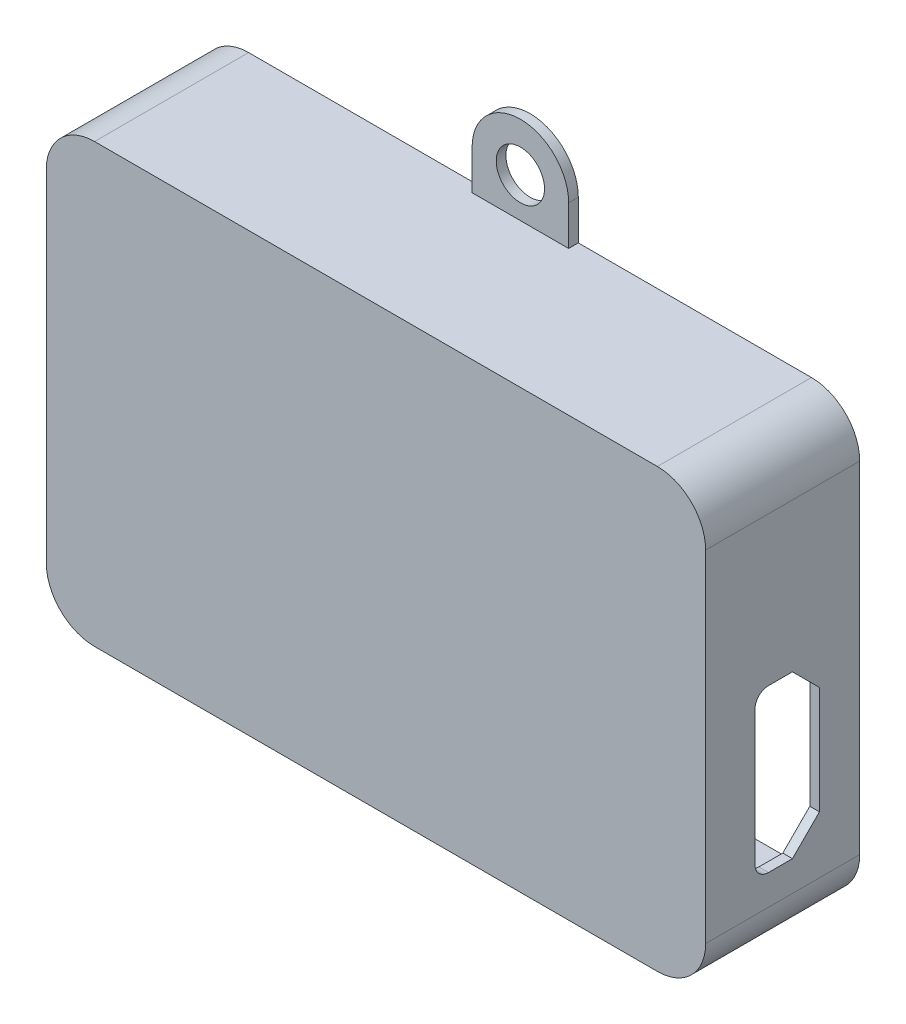
SolidWorks part; units mm, degrees
ref_plane "Front Plane" through (0, 0, 0) normal (0, 0, 1) x (1, 0, 0)
ref_plane "Top Plane" through (0, 0, 0) normal (0, 1, 0) x (1, 0, 0)
ref_plane "Right Plane" through (0, 0, 0) normal (1, 0, 0) x (0, 0, -1)
sketch "Sketch1" plane through (0, 0, 0) normal (0, 0, 1) x (1, 0, 0)
  line L1 (-14.575, -11.325) -> (14.575, -11.325)
  line L2 (-17.075, -8.825) -> (-17.075, 8.825)
  line L3 (-14.575, 11.325) -> (14.575, 11.325)
  line L4 (17.075, -8.825) -> (17.075, 8.825)
  line L5 (-17.075, -11.325) -> (17.075, 11.325) construction
  line L6 (-17.075, 11.325) -> (17.075, -11.325) construction
  line L8 (-16.575, 10.825) -> (-17.075, 10.825) construction
  line L9 (14.575, -10.825) -> (-14.575, -10.825)
  line L10 (16.575, -8.825) -> (16.575, 8.825)
  line L11 (14.575, 10.825) -> (-14.575, 10.825)
  line L12 (-16.575, -8.825) -> (-16.575, 8.825)
  line L13 (16.575, -10.825) -> (-16.575, 10.825) construction
  line L14 (16.575, 10.825) -> (-16.575, -10.825) construction
  line L15 (-16.575, 10.825) -> (-16.575, 11.325) construction
  line L16 (-16.375, 9.825) -> (-16.375, -9.825) construction
  line L17 (16.375, 9.825) -> (-16.375, 9.825) construction
  line L18 (-2.5, 13.375) -> (-2.5, 11.325)
  line L19 (2.5, 13.375) -> (2.5, 11.325)
  line L20 (-2.5, -13.375) -> (-2.5, -11.325)
  line L21 (2.5, -13.375) -> (2.5, -11.325)
  line L22 (-20.75, 2.5) -> (-17.075, 2.5)
  line L23 (-20.75, -2.5) -> (-17.075, -2.5)
  arc A0 (-14.575, -10.825) -> (-16.575, -8.825) centre (-14.575, -8.825) cw
  arc A1 (-2.4744, -13.0179) -> (2.4744, -13.0179) centre (0, -13.375) ccw construction
  arc A2 (14.575, -10.825) -> (16.575, -8.825) centre (14.575, -8.825) ccw
  arc A3 (16.575, 8.825) -> (14.575, 10.825) centre (14.575, 8.825) ccw
  arc A4 (-20.3929, 2.4744) -> (-20.3929, -2.4744) centre (-20.75, 0) ccw construction
  arc A5 (-14.575, 10.825) -> (-16.575, 8.825) centre (-14.575, 8.825) ccw
  arc A6 (-14.575, -11.325) -> (-17.075, -8.825) centre (-14.575, -8.825) cw
  arc A7 (14.575, -11.325) -> (17.075, -8.825) centre (14.575, -8.825) ccw
  arc A8 (2.4744, 13.0179) -> (-2.4744, 13.0179) centre (0, 13.375) ccw construction
  circle A9 centre (-20.75, 0) radius 1.25
  arc A10 (-2.4744, -13.0179) -> (2.4744, -13.0179) centre (0, -13.375) ccw
  circle A11 centre (0, 13.375) radius 1.25
  circle A12 centre (0, -13.375) radius 1.25
  arc A13 (-20.3929, 2.4744) -> (-20.3929, -2.4744) centre (-20.75, 0) ccw
  arc A14 (14.575, 11.325) -> (17.075, 8.825) centre (14.575, 8.825) cw
  arc A15 (-17.075, 8.825) -> (-14.575, 11.325) centre (-14.575, 8.825) cw
  arc A17 (2.4744, 13.0179) -> (-2.4744, 13.0179) centre (0, 13.375) ccw
  point P0 (0, 0)
  point P31 (0, 0)
  dimension "D4" = 2.5
  dimension "D5" = 2
  dimension "D6" = 2.5
  dimension "D1" = 0.5
  dimension "D2" = 0.2
  dimension "D3" = 1
extrude "Boss-Extrude1" add sketch "Sketch1" along normal offset from surface (7.48 mm away) 2.5 contours A13 L2 | L1 L4 L3 L2 L9 L12 L11 L10 | A17 L3 | A10 L1 region at (-16.053, -10.303, 0) region at (0, -11.3926, 0) region at (-18.9125, -2.4205, 0) region at (-2.4324, 12.35, 0) offset beyond the face yes
sketch "Sketch2" plane through (0, 0, 7.48) normal (0, 0, 1) x (1, 0, 0)
  line L0 (-2.5, 11.325) -> (2.5, 11.325)
  line L1 (-17.075, 2.5) -> (-17.075, -2.5)
  line L2 (-2.5, -11.325) -> (2.5, -11.325)
  line L13 (-17.075, 2.5) -> (-20.75, 2.5)
  line L14 (-20.75, -2.5) -> (-17.075, -2.5)
  line L15 (-17.075, -2.5) -> (-17.075, -8.825)
  line L16 (-14.575, -11.325) -> (-2.5, -11.325)
  line L17 (-2.5, -11.325) -> (-2.5, -13.375)
  line L18 (2.5, -13.375) -> (2.5, -11.325)
  line L19 (2.5, -11.325) -> (14.575, -11.325)
  line L20 (17.075, -8.825) -> (17.075, 8.825)
  line L21 (14.575, 11.325) -> (2.5, 11.325)
  line L22 (2.5, 11.325) -> (2.5, 13.375)
  line L23 (-2.5, 13.375) -> (-2.5, 11.325)
  line L24 (-2.5, 11.325) -> (-14.575, 11.325)
  line L25 (-17.075, 8.825) -> (-17.075, 2.5)
  line L26 (-17.075, 2.5) -> (-20.75, 2.5)
  line L27 (-20.75, -2.5) -> (-17.075, -2.5)
  line L28 (-17.075, -2.5) -> (-17.075, -8.825)
  line L29 (-14.575, -11.325) -> (-2.5, -11.325)
  line L30 (-2.5, -11.325) -> (-2.5, -13.375)
  line L31 (2.5, -13.375) -> (2.5, -11.325)
  line L32 (2.5, -11.325) -> (14.575, -11.325)
  line L33 (17.075, -8.825) -> (17.075, 8.825)
  line L34 (14.575, 11.325) -> (2.5, 11.325)
  line L35 (2.5, 11.325) -> (2.5, 13.375)
  line L36 (-2.5, 13.375) -> (-2.5, 11.325)
  line L37 (-2.5, 11.325) -> (-14.575, 11.325)
  line L38 (-17.075, 8.825) -> (-17.075, 2.5)
  arc A7 (-20.75, 2.5) -> (-20.75, -2.5) centre (-20.75, 0) ccw
  arc A8 (-17.075, -8.825) -> (-14.575, -11.325) centre (-14.575, -8.825) ccw
  arc A9 (-2.5, -13.375) -> (2.5, -13.375) centre (0, -13.375) ccw
  arc A10 (14.575, -11.325) -> (17.075, -8.825) centre (14.575, -8.825) ccw
  arc A11 (17.075, 8.825) -> (14.575, 11.325) centre (14.575, 8.825) ccw
  arc A12 (2.5, 13.375) -> (-2.5, 13.375) centre (0, 13.375) ccw
  arc A13 (-14.575, 11.325) -> (-17.075, 8.825) centre (-14.575, 8.825) ccw
  arc A14 (-20.75, 2.5) -> (-20.75, -2.5) centre (-20.75, 0) ccw
  arc A15 (-17.075, -8.825) -> (-14.575, -11.325) centre (-14.575, -8.825) ccw
  arc A16 (-2.5, -13.375) -> (2.5, -13.375) centre (0, -13.375) ccw
  arc A17 (14.575, -11.325) -> (17.075, -8.825) centre (14.575, -8.825) ccw
  arc A18 (17.075, 8.825) -> (14.575, 11.325) centre (14.575, 8.825) ccw
  arc A19 (2.5, 13.375) -> (-2.5, 13.375) centre (0, 13.375) ccw
  arc A20 (-14.575, 11.325) -> (-17.075, 8.825) centre (-14.575, 8.825) ccw
  arc M18 (-20.75, 2.5) -> (-20.75, -2.5) centre (-20.75, 0) ccw
  arc M23 (-2.5, -13.375) -> (2.5, -13.375) centre (0, -13.375) ccw
  arc M29 (2.5, 13.375) -> (-2.5, 13.375) centre (0, 13.375) ccw
  circle M57 centre (0, 13.375) radius 1.25
  circle M62 centre (-20.75, 0) radius 1.25
  line M63 (-17.075, 2.5) -> (-20.75, 2.5)
  line M64 (-20.75, -2.5) -> (-17.075, -2.5)
  line M68 (-2.5, -11.325) -> (-2.5, -13.375)
  line M69 (2.5, -13.375) -> (2.5, -11.325)
  line M74 (2.5, 11.325) -> (2.5, 13.375)
  line M75 (-2.5, 13.375) -> (-2.5, 11.325)
  circle M79 centre (0, -13.375) radius 1.25
  dimension "D1" = 0
extrude "Cut-Extrude1" cut sketch "Sketch2" against normal offset from surface (6.98 mm away) 0.5 contours L0 M75 M74 M29 M57 | L1 M63 M18 M64 M62 | L2 M68 M23 M69 M79 region at (-2.4324, 12.35, 7.48) region at (-17.1545, 0, 7.48) region at (2.4324, -12.35, 7.48) up to face at (-3.9075, 0, 0)
sketch "Sketch3" plane through (17.075, 0, 0) normal (1, 0, 0) x (0, 0, -1)
  line L0 (-3.98, -7.065) -> (-4.18, -7.065) construction
  line L1 (-5.425, -7.265) -> (-2.085, -7.265)
  line L2 (-5.425, -7.265) -> (-5.425, 1.115)
  line L3 (-5.425, 1.115) -> (-2.085, 1.115)
  line L4 (-2.085, -7.265) -> (-2.085, 1.115)
  line L5 (-5.225, -6.075) -> (-5.425, -6.075) construction
  line L6 (-4.18, -7.065) -> (-4.18, -7.265) construction
  line L7 (-4.18, 0.915) -> (-4.18, 1.115) construction
  line L8 (-2.285, -5.375) -> (-2.085, -5.375) construction
  dimension "D1" = 0.2
extrude "Cut-Extrude2" cut sketch "Sketch3" against normal up to next
chamfer "Chamfer1" distance 1.4 angle 45 2 edges at (16.825, 1.115, 2.085) (16.825, -7.265, 2.085)
fillet "Fillet1" radius 0.7 2 edges at (16.825, 1.115, 5.425) (16.825, -7.265, 5.425)
sketch "Sketch4" plane through (0, 0, 7.48) normal (0, 0, 1) x (1, 0, 0)
  line L4 (-17.075, 8.825) -> (-17.075, -8.825)
  line L5 (-14.575, -11.325) -> (14.575, -11.325)
  line L6 (17.075, -8.825) -> (17.075, 8.825)
  line L7 (14.575, 11.325) -> (-14.575, 11.325)
  line L8 (-17.075, 8.825) -> (-17.075, -8.825)
  line L9 (-14.575, -11.325) -> (14.575, -11.325)
  line L10 (17.075, -8.825) -> (17.075, 8.825)
  line L11 (14.575, 11.325) -> (-14.575, 11.325)
  arc A4 (-17.075, -8.825) -> (-14.575, -11.325) centre (-14.575, -8.825) ccw
  arc A5 (14.575, -11.325) -> (17.075, -8.825) centre (14.575, -8.825) ccw
  arc A6 (17.075, 8.825) -> (14.575, 11.325) centre (14.575, 8.825) ccw
  arc A7 (-14.575, 11.325) -> (-17.075, 8.825) centre (-14.575, 8.825) ccw
  arc A8 (-17.075, -8.825) -> (-14.575, -11.325) centre (-14.575, -8.825) ccw
  arc A9 (14.575, -11.325) -> (17.075, -8.825) centre (14.575, -8.825) ccw
  arc A10 (17.075, 8.825) -> (14.575, 11.325) centre (14.575, 8.825) ccw
  arc A11 (-14.575, 11.325) -> (-17.075, 8.825) centre (-14.575, 8.825) ccw
  dimension "D1" = 0
extrude "Boss-Extrude2" add sketch "Sketch4" along normal blind 0.5
sketch "Sketch5" [suppressed] plane through (0, 0, 0.5) normal (0, 0, 1) x (1, 0, 0)
  line L0 (2.5, -13.375) -> (2.5, -11.325) construction
  line L1 (2.5, -11.325) -> (-2.5, -11.325) construction
  line L2 (-2.5, -11.325) -> (-2.5, -13.375) construction
  line L3 (-2.5, 13.375) -> (-2.5, 11.325) construction
  line L4 (-2.5, 11.325) -> (2.5, 11.325) construction
  line L5 (2.5, 11.325) -> (2.5, 13.375) construction
  line L6 (-20.75, -2.5) -> (-17.075, -2.5) construction
  line L7 (-17.075, -2.5) -> (-17.075, 2.5) construction
  line L8 (-17.075, 2.5) -> (-20.75, 2.5) construction
  line L9 (2.5, -13.375) -> (2.5, -11.325)
  line L10 (2.5, -11.325) -> (-2.5, -11.325)
  line L11 (-2.5, -11.325) -> (-2.5, -13.375)
  line L12 (-2.5, 13.375) -> (-2.5, 11.325)
  line L13 (-2.5, 11.325) -> (2.5, 11.325)
  line L14 (2.5, 11.325) -> (2.5, 13.375)
  line L15 (-20.75, -2.5) -> (-17.075, -2.5)
  line L16 (-17.075, -2.5) -> (-17.075, 2.5)
  line L17 (-17.075, 2.5) -> (-20.75, 2.5)
  line L18 (-2.5, 11.825) -> (2.5, 11.825)
  line L19 (-20.75, 2) -> (-20.75, 2.5) construction
  line L20 (0, 11.825) -> (0, 11.325) construction
  line L21 (-17.075, 0) -> (17.075, 0) construction
  line L22 (17.075, -8.825) -> (17.075, 8.825) construction
  line L23 (-2.5, -11.825) -> (2.5, -11.825)
  arc A0 (-2.5, -13.375) -> (2.5, -13.375) centre (0, -13.375) ccw construction
  arc A1 (2.5, 13.375) -> (-2.5, 13.375) centre (0, 13.375) ccw construction
  arc A2 (-20.75, 2.5) -> (-20.75, -2.5) centre (-20.75, 0) ccw construction
  arc A3 (-2.5, -13.375) -> (2.5, -13.375) centre (0, -13.375) ccw
  arc A4 (2.5, 13.375) -> (-2.5, 13.375) centre (0, 13.375) ccw
  arc A5 (-20.75, 2.5) -> (-20.75, -2.5) centre (-20.75, 0) ccw
  circle A6 centre (-20.75, 0) radius 2
  circle A7 centre (-20.75, 0) radius 2.5
  circle A8 centre (0, 13.375) radius 2.5
  circle A9 centre (0, -13.375) radius 2.5
  circle A10 centre (0, 13.375) radius 2
  circle A11 centre (0, -13.375) radius 2
  arc M9 (-20.75, 2.5) -> (-20.75, -2.5) centre (-20.75, 0) ccw
  dimension "D1" = 0.5
extrude "Boss-Extrude3" [suppressed] add sketch "Sketch5" along normal up to surface (7.48 mm away) contours A10 L18 A8 A4 | A7 A6 M9 | A11 L23 A9 A3 up to face at (0, 0, 7.98)
sketch "Sketch6" plane through (0, 0, 7.48) normal (0, 0, -1) x (-1, 0, 0)
  line L1 (-14.575, -10.825) -> (-16.575, -10.825)
  line L2 (-14.575, -10.825) -> (-14.575, -9.325)
  line L3 (-14.575, -9.325) -> (-16.575, -9.325)
  line L4 (16.575, -8.825) -> (16.575, 8.825)
  line L5 (14.575, 10.825) -> (-14.575, 10.825)
  line L6 (-16.575, 8.825) -> (-16.575, -8.825)
  line L7 (-14.575, -10.825) -> (14.575, -10.825)
  line L8 (16.575, -8.825) -> (16.575, 8.825)
  line L9 (14.575, 10.825) -> (-14.575, 10.825)
  line L10 (-16.575, 8.825) -> (-16.575, -8.825)
  line L11 (-14.575, -10.825) -> (14.575, -10.825)
  line L12 (-16.575, -10.825) -> (-16.575, -9.325)
  line L13 (-16.575, 1.915) -> (-14.575, 1.915)
  line L14 (-16.575, 1.915) -> (-16.575, 3.415)
  line L15 (-16.575, 3.415) -> (-14.575, 3.415)
  line L16 (-14.575, 1.915) -> (-14.575, 3.415)
  line L17 (-14.575, 10.825) -> (-16.575, 10.825)
  line L18 (-14.575, 10.825) -> (-14.575, 9.325)
  line L19 (-14.575, 9.325) -> (-16.575, 9.325)
  line L20 (-16.575, 10.825) -> (-16.575, 9.325)
  line L21 (16.575, 10.825) -> (14.575, 10.825)
  line L22 (16.575, 10.825) -> (16.575, 9.325)
  line L23 (16.575, 9.325) -> (14.575, 9.325)
  line L24 (14.575, 10.825) -> (14.575, 9.325)
  line L25 (10.575, -10.825) -> (7.575, -10.825)
  line L26 (10.575, -10.825) -> (10.575, -9.325)
  line L27 (10.575, -9.325) -> (7.575, -9.325)
  line L28 (7.575, -10.825) -> (7.575, -9.325)
  arc A4 (14.575, -10.825) -> (16.575, -8.825) centre (14.575, -8.825) ccw
  arc A5 (16.575, 8.825) -> (14.575, 10.825) centre (14.575, 8.825) ccw
  arc A6 (-14.575, 10.825) -> (-16.575, 8.825) centre (-14.575, 8.825) ccw
  arc A7 (-16.575, -8.825) -> (-14.575, -10.825) centre (-14.575, -8.825) ccw
  arc A8 (14.575, -10.825) -> (16.575, -8.825) centre (14.575, -8.825) ccw
  arc A9 (16.575, 8.825) -> (14.575, 10.825) centre (14.575, 8.825) ccw
  arc A10 (-14.575, 10.825) -> (-16.575, 8.825) centre (-14.575, 8.825) ccw
  arc A11 (-16.575, -8.825) -> (-14.575, -10.825) centre (-14.575, -8.825) ccw
  arc M24 (16.575, 8.825) -> (14.575, 10.825) centre (14.575, 8.825) ccw
  arc M26 (-14.575, 10.825) -> (-16.575, 8.825) centre (-14.575, 8.825) ccw
  arc M28 (-16.575, -8.825) -> (-14.575, -10.825) centre (-14.575, -8.825) ccw
  dimension "D2" = 1.5
  dimension "D3" = 1.5
  dimension "D5" = 3
  dimension "D6" = 6
  dimension "D1" = 0
extrude "Boss-Extrude4" add sketch "Sketch6" along normal offset from surface (4.98 mm away) 2.5 contours L28 L11 L26 L27 | L2 L3 M28 | L13 L16 L15 L10 | L19 L18 M26 | L24 L23 M24 region at (15.3591, -9.9498, 7.48) region at (-9.075, -10.075, 7.48) region at (15.575, 2.665, 7.48) region at (-15.3591, 9.9498, 7.48) region at (15.3591, 9.9498, 7.48) up to face at (-3.9075, 0, 0)
sketch "Sketch7" plane through (0, 0, 7.48) normal (0, 0, -1) x (-1, 0, 0)
  line L0 (16.575, -8.825) -> (16.575, 8.825) construction
  line L1 (16.575, 4.185) -> (10.655, 4.185)
  line L2 (16.575, 4.185) -> (16.575, 6.185)
  line L3 (16.575, 6.185) -> (10.655, 6.185)
  line L4 (10.655, 4.185) -> (10.655, 6.185)
  line L5 (17.075, 3.985) -> (10.855, 3.985) construction
  line L6 (10.855, 3.985) -> (10.855, 4.185) construction
  line L7 (10.655, 2.5) -> (6.055, 2.5)
  line L8 (10.655, 2.5) -> (10.655, 4.5)
  line L9 (10.655, 4.5) -> (6.055, 4.5)
  line L10 (6.055, 2.5) -> (6.055, 4.5)
  line L11 (10.855, 3.985) -> (10.655, 3.985) construction
  line L12 (10.655, 2.5) -> (10.655, 2.3) construction
  line L13 (10.855, 2.3) -> (6.255, 2.3) construction
  line L14 (6.255, 2.3) -> (6.055, 2.3) construction
  line L15 (6.055, 3.8) -> (4.055, 3.8)
  line L16 (6.055, 3.8) -> (6.055, 1.8)
  line L17 (6.055, 1.8) -> (4.055, 1.8)
  line L18 (4.055, 3.8) -> (4.055, 1.8)
  line L19 (-5.1149, 0) -> (3.3954, 0) construction
  line L20 (16.575, -4.185) -> (16.575, -6.185)
  line L21 (16.575, -6.185) -> (10.655, -6.185)
  line L22 (16.575, -4.185) -> (10.655, -4.185)
  line L23 (10.655, -4.185) -> (10.655, -6.185)
  line L24 (10.655, -2.5) -> (10.655, -4.5)
  line L25 (10.655, -4.5) -> (6.055, -4.5)
  line L26 (6.055, -2.5) -> (6.055, -4.5)
  line L27 (10.655, -2.5) -> (6.055, -2.5)
  line L28 (6.055, -3.8) -> (6.055, -1.8)
  line L29 (6.055, -3.8) -> (4.055, -3.8)
  line L30 (4.055, -3.8) -> (4.055, -1.8)
  line L31 (6.055, -1.8) -> (4.055, -1.8)
  line M32 (16.575, -8.825) -> (16.575, 8.825)
  dimension "D1" = 0.2
  dimension "D2" = 2
  dimension "D3" = 0.5
extrude "Boss-Extrude5" add sketch "Sketch7" along normal blind 2.5 contours L4 L1 L3 M32 | L10 L7 L8 L4 L9 | L15 L18 L17 L16 L10 | L28 L31 L30 L29 L26 | L24 L27 L26 L25 L23 | L22 L23 L21 M32 region at (-13.615, 5.185, 7.48) region at (-13.615, -5.185, 7.48) region at (-8.355, 3.5, 7.48) region at (-8.355, -3.5, 7.48) region at (-5.055, 2.8, 7.48) region at (-5.055, -2.8, 7.48)
sketch "Sketch8" plane through (-17.075, 0, 0) normal (-1, 0, 0) x (0, 0, 1)
  line L0 (7.48, -4.185) -> (7.48, 4.185) construction
  line L1 (7.48, -4.185) -> (4.88, -4.185)
  line L2 (7.48, -4.185) -> (7.48, 4.185)
  line L3 (7.48, 4.185) -> (4.88, 4.185)
  line L4 (4.88, -4.185) -> (4.88, 4.185)
  line L5 (4.98, 4.185) -> (7.48, 4.185) construction
  line L6 (4.98, -4.185) -> (7.48, -4.185) construction
  dimension "D1" = 2.6
extrude "Cut-Extrude3" cut sketch "Sketch8" against normal up to next
